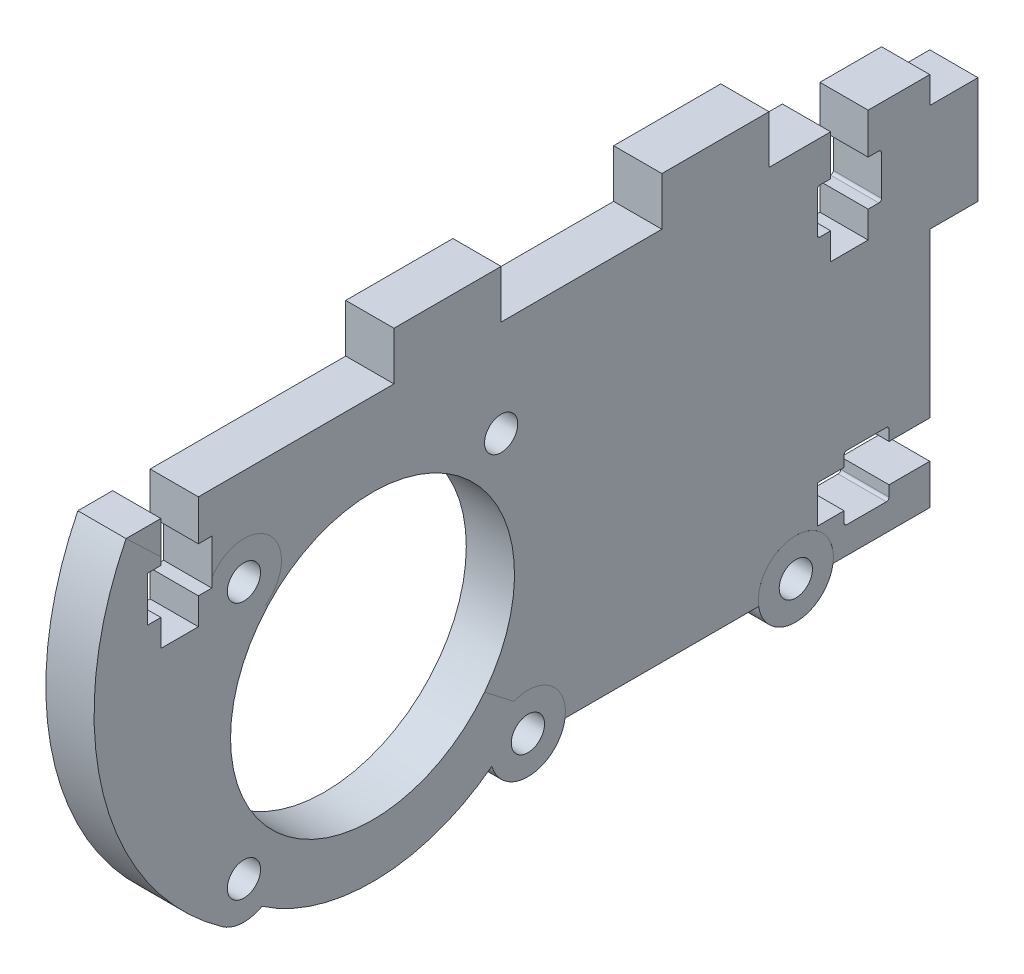
SolidWorks part; units mm, degrees
ref_plane "Front Plane" through (0, 0, 0) normal (0, 0, 1) x (1, 0, 0)
ref_plane "Top Plane" through (0, 0, 0) normal (0, 1, 0) x (1, 0, 0)
ref_plane "Right Plane" through (0, 0, 0) normal (1, 0, 0) x (0, 0, -1)
sketch "Sketch1" plane through (0, 0, 0) normal (1, 0, 0) x (0, 0, -1)
  line L0 (0, 0) -> (0, -35)
  line L1 (0, -35) -> (-75, 0)
  line L2 (-75, 0) -> (0, 0)
  dimension "D1" = 35
  dimension "D2" = 75
extrude "Boss-Extrude1" add sketch "Sketch1" along normal blind 4.5
sketch "Sketch2" plane through (4.5, 0, 0) normal (1, 0, 0) x (0, 0, -1)
  line L0 (0, -35) -> (0, 0) construction
  line L1 (-4.5, -2.5) -> (4.5, -2.5)
  line L2 (-4.5, -2.5) -> (-4.5, -12.5)
  line L3 (-4.5, -12.5) -> (4.5, -12.5)
  line L4 (4.5, -2.5) -> (4.5, -12.5)
  line L5 (-4.5, -2.5) -> (4.5, -12.5) construction
  line L6 (-4.5, -12.5) -> (4.5, -2.5) construction
  line L7 (0, 0) -> (-75, 0) construction
  point P0 (0, -7.5)
  dimension "D1" = 10
  dimension "D2" = 7.5
  dimension "D3" = 4.5
extrude "Boss-Extrude2" add sketch "Sketch2" against normal through all
sketch "Sketch3" plane through (4.5, 0, 0) normal (1, 0, 0) x (0, 0, -1)
  line L0 (0, -35) -> (-40, -35)
  line L1 (0, -25) -> (-75, 0)
  line L4 (0, -35) -> (0, -12.5) construction
  line L5 (0, -25) -> (0, -35)
  line L6 (-75, 0) -> (-40, -35)
  dimension "D1" = 40
  dimension "D2" = 10
extrude "Boss-Extrude3" add sketch "Sketch3" against normal through all
sketch "Sketch4" plane through (4.5, 0, 0) normal (1, 0, 0) x (0, 0, -1)
  line L0 (0, -29.5) -> (-10.5, -29.5) construction
  line L1 (0, -35) -> (0, -12.5) construction
  line L2 (0, -27.75) -> (-10.5, -27.75) construction
  line L3 (-10.5, -27.75) -> (-10.5, -31.25) construction
  line L4 (0, -31.25) -> (0, -27.75)
  line L5 (0, -27.75) -> (-3.8, -27.75)
  line L6 (-3.8, -27.75) -> (-3.8, -26.75)
  line L7 (-4.05, -26.5) -> (-7.75, -26.5)
  line L8 (-8, -26.75) -> (-8, -27.75)
  line L9 (-8, -27.75) -> (-10.5, -27.75)
  line L10 (-10.5, -27.75) -> (-10.5, -31.25)
  line L12 (0, -31.25) -> (-10.5, -31.25) construction
  line L13 (-8, -31.25) -> (-10.5, -31.25)
  line L14 (-8, -32.25) -> (-8, -31.25)
  line L15 (-4.05, -32.5) -> (-7.75, -32.5)
  line L16 (-3.8, -31.25) -> (-3.8, -32.25)
  line L17 (0, -31.25) -> (-3.8, -31.25)
  line L18 (4.5, -12.5) -> (4.5, -2.5) construction
  line L19 (0, -18.5) -> (-56.5, -18.5) construction
  line L20 (-75, 0) -> (-40, -35) construction
  line L37 (0, -31.25) -> (-10.5, -31.25) construction
  arc A0 (-8, -32.25) -> (-7.75, -32.5) centre (-7.75, -32.25) ccw
  arc A1 (-4.05, -32.5) -> (-3.8, -32.25) centre (-4.05, -32.25) ccw
  arc A2 (-3.8, -26.75) -> (-4.05, -26.5) centre (-4.05, -26.75) ccw
  arc A3 (-7.75, -26.5) -> (-8, -26.75) centre (-7.75, -26.75) ccw
  point P10 (4.5, -7.5)
  point P20 (-8, -32.5)
  point P23 (-3.8, -32.5)
  point P26 (-3.8, -26.5)
  point P29 (-8, -26.5)
  dimension "D7" = 0.25
  dimension "D1" = 10.5
  dimension "D2" = 1.75
  dimension "D3" = 3
  dimension "D4" = 4.2
  dimension "D5" = 8
  dimension "D6" = 22
extrude "Cut-Extrude1" cut sketch "Sketch4" against normal through all
sketch "Sketch5" plane through (4.5, 0, 0) normal (1, 0, 0) x (0, 0, -1)
  line L0 (0, 0) -> (-75, 0) construction
  line L1 (-25, 4.5) -> (-15, 4.5)
  line L2 (-25, 4.5) -> (-25, 0)
  line L3 (0, 0) -> (-75, 0) construction
  line L4 (-15, 4.5) -> (-15, 0)
  line L5 (-25, 4.5) -> (-20, 0) construction
  line L6 (-20, 0) -> (-15, 4.5) construction
  line L7 (-32.5, 0) -> (-32.5, 4.5) construction
  line L8 (-45, 0) -> (-50, 4.5) construction
  line L9 (-40, 4.5) -> (-45, 0) construction
  line L10 (-50, 4.5) -> (-50, 0)
  line L12 (-40, 4.5) -> (-40, 0)
  line L13 (-40, 4.5) -> (-50, 4.5)
  line L14 (-20, 0) -> (-15, 4.5) construction
  line L15 (-15, 0) -> (-25, 0)
  line L16 (-40, 0) -> (-50, 0)
  point P0 (-20, 0)
  point P14 (-45, 0)
  dimension "D3" = 4.5
  dimension "D1" = 20
  dimension "D2" = 10
  dimension "D4" = 25
  dimension "D5" = 5
extrude "Boss-Extrude4" add sketch "Sketch5" against normal through all
sketch "Sketch8" [suppressed] plane through (4.5, 0, 0) normal (1, 0, 0) x (0, 0, -1)
  line L0 (-15, -30) -> (-27, -30) construction
  line L1 (-15, -35) -> (-27, -35)
  line L2 (-15, -25) -> (-27, -25)
  line L3 (-15, -35) -> (0, -35) construction
  line L4 (-15, -25) -> (-15, -35)
  arc A1 (-27, -25) -> (-27, -35) centre (-27, -30) ccw
  dimension "D5" = 5
  dimension "D1" = 0
  dimension "D2" = 12
  dimension "D3" = 0
  dimension "D4" = 10
extrude "Boss-Extrude5" [suppressed] add sketch "Sketch8" against normal up to surface (4.5 mm away) up to face at (0, -17.3125, 13.4469)
sketch "Sketch9" [suppressed] plane through (4.5, 0, 0) normal (1, 0, 0) x (0, 0, -1)
  line L0 (-27, -30) -> (-22, -30) construction
  line L1 (-27, -27) -> (-22, -27)
  line L2 (-27, -33) -> (-22, -33)
  arc A0 (-27, -27) -> (-27, -33) centre (-27, -30) ccw
  arc A1 (-22, -33) -> (-22, -27) centre (-22, -30) ccw
  point P3 (-24.5, -30)
  dimension "D1" = 3
  dimension "D2" = 5
extrude "Cut-Extrude3" [suppressed] cut sketch "Sketch9" against normal through all
sketch "Sketch10" plane through (0, 0, 0) normal (-1, 0, 0) x (0, 0, 1)
  line L0 (40, -35) -> (75, -12)
  line L1 (75, -12) -> (75, 0)
  line L3 (75, 0) -> (40, -35)
  dimension "D1" = 12
extrude "Boss-Extrude6" [suppressed] add sketch "Sketch10" against normal through all
sketch "Sketch6" plane through (4.5, 0, 0) normal (1, 0, 0) x (0, 0, -1)
  line L0 (-32.5, 0) -> (-32.5, -10.5) construction
  line L1 (-25, 0) -> (-40, 0) construction
  line L2 (-30.75, -10.5) -> (-34.25, -10.5) construction
  line L3 (-34.25, -10.5) -> (-34.25, 0) construction
  line L4 (-30.75, 0) -> (-34.25, 0)
  line L5 (-34.25, 0) -> (-34.25, -3.8)
  line L6 (-34.25, -3.8) -> (-35.25, -3.8)
  line L7 (-35.5, -4.05) -> (-35.5, -7.75)
  line L8 (-35.25, -8) -> (-34.25, -8)
  line L9 (-34.25, -8) -> (-34.25, -10.5)
  line L10 (-34.25, -10.5) -> (-30.75, -10.5)
  line L11 (-30.75, -10.5) -> (-30.75, 0) construction
  line L12 (-30.75, -8) -> (-30.75, -10.5)
  line L13 (-29.75, -8) -> (-30.75, -8)
  line L14 (-29.5, -4.05) -> (-29.5, -7.75)
  line L15 (-30.75, -3.8) -> (-29.75, -3.8)
  line L16 (-30.75, 0) -> (-30.75, -3.8)
  arc A0 (-35.5, -7.75) -> (-35.25, -8) centre (-35.25, -7.75) ccw
  arc A1 (-35.25, -3.8) -> (-35.5, -4.05) centre (-35.25, -4.05) ccw
  arc A2 (-29.75, -3.8) -> (-29.5, -4.05) centre (-29.75, -4.05) cw
  arc A3 (-29.5, -7.75) -> (-29.75, -8) centre (-29.75, -7.75) cw
  point P12 (-35.5, -8)
  point P15 (-35.5, -3.8)
  point P26 (-29.5, -3.8)
  point P27 (-29.5, -8)
  dimension "D1" = 10.5
  dimension "D2" = 1.75
  dimension "D4" = 4.2
  dimension "D6" = 0.25
  dimension "D3" = 8
  dimension "D5" = 3
extrude "Cut-Extrude2" [suppressed] cut sketch "Sketch6" against normal through all
sketch "Sketch11" plane through (0, 0, 0) normal (-1, 0, 0) x (0, 0, 1)
  line L0 (7.5, 0) -> (7.5, -10.5) construction
  line L1 (0, 0) -> (15, 0) construction
  line L2 (5.75, -10.5) -> (9.25, -10.5)
  line L3 (9.25, -10.5) -> (9.25, -8)
  line L4 (9.25, -8) -> (10.25, -8)
  line L5 (10.5, -7.75) -> (10.5, -4.05)
  line L6 (10.25, -3.8) -> (9.25, -3.8)
  line L7 (9.25, -3.8) -> (9.25, 0)
  line L8 (9.25, 0) -> (5.75, 0)
  line L9 (9.25, -8) -> (9.25, -3.8) construction
  line L10 (0, 0) -> (15, 0) construction
  line L11 (5.75, -8) -> (5.75, -3.8) construction
  line L12 (5.75, -3.8) -> (5.75, 0)
  line L13 (4.75, -3.8) -> (5.75, -3.8)
  line L14 (4.5, -7.75) -> (4.5, -4.05)
  line L15 (5.75, -8) -> (4.75, -8)
  line L16 (5.75, -10.5) -> (5.75, -8)
  arc A0 (10.5, -4.05) -> (10.25, -3.8) centre (10.25, -4.05) ccw
  arc A1 (4.75, -3.8) -> (4.5, -4.05) centre (4.75, -4.05) ccw
  arc A2 (10.25, -8) -> (10.5, -7.75) centre (10.25, -7.75) ccw
  arc A3 (4.5, -7.75) -> (4.75, -8) centre (4.75, -7.75) ccw
  point P11 (7.5, 0)
  point P22 (10.5, -3.8)
  point P25 (4.5, -3.8)
  point P28 (10.5, -8)
  point P31 (4.5, -8)
  dimension "D7" = 0.25
  dimension "D1" = 10.5
  dimension "D3" = 3
  dimension "D8" = 0.25
  dimension "D2" = 4.2
  dimension "D4" = 8
  dimension "D5" = 1.75
  dimension "D6" = 0
extrude "Cut-Extrude4" cut sketch "Sketch11" against normal through all
sketch "Sketch12" plane through (0, 0, 0) normal (-1, 0, 0) x (0, 0, 1)
  line L0 (52, -21) -> (40, -9) construction
  line L1 (52, -21) -> (52, -7.75) construction
  line L2 (52, -21) -> (64, -9) construction
  line L3 (52, -21) -> (38.75, -21) construction
  line L4 (52, -21) -> (40, -33) construction
  line L5 (52, -21) -> (40, -9) construction
  line L6 (0, -27.75) -> (0, -12.5) construction
  line L7 (25, 0) -> (40, 0) construction
  circle A0 centre (52, -21) radius 13.25
  circle A1 centre (40, -9) radius 1.55
  circle A2 centre (64, -9) radius 1.55
  circle A3 centre (40, -33) radius 1.55
  dimension "D1" = 26.5
  dimension "D2" = 3.1
  dimension "D3" = 12
  dimension "D4" = 45
  dimension "D5" = 52
  dimension "D6" = 21
extrude "Cut-Extrude5" cut sketch "Sketch12" against normal through all
sketch "Sketch13" plane through (0, 0, 0) normal (-1, 0, 0) x (0, 0, 1)
  line L0 (61.7849, -12.0659) -> (65.4774, -8.6946)
  line L1 (41.5411, -29.1347) -> (37.5943, -32.2044)
  line L2 (0, -35) -> (100, -35) construction
  line L6 (52, -21) -> (75, 0) construction
  line L7 (52, -21) -> (34, -35) construction
  arc A0 (41.5411, -29.1347) -> (61.7849, -12.0659) centre (52, -21) ccw
  arc A1 (37.5943, -32.2044) -> (65.4774, -8.6946) centre (52, -21) ccw
  circle A3 centre (52, -21) radius 13.25 construction
  dimension "D1" = 5
  dimension "D2" = 100
  dimension "D3" = 18
extrude "Boss-Extrude7" add sketch "Sketch13" against normal through all
sketch "Sketch14" plane through (0, 0, 0) normal (-1, 0, 0) x (0, 0, 1)
  line L0 (52, -7.75) -> (52, -34.25) construction
  line L1 (52, -21) -> (64, -33) construction
  circle A1 centre (64, -33) radius 3.5
  arc A3 (61.7849, -12.0659) -> (41.5411, -29.1347) centre (52, -21) ccw construction
  dimension "D2" = 7
  dimension "D1" = 45
  dimension "D3" = 12
extrude "Boss-Extrude8" add sketch "Sketch14" against normal through all
sketch "Sketch15" plane through (0, 0, 0) normal (-1, 0, 0) x (0, 0, 1)
  line L0 (66.4749, -35.4749) -> (52, -21) construction
  circle A1 centre (64, -33) radius 1.55
  arc A2 (62.305, -36.0622) -> (67.0622, -31.305) centre (64, -33) ccw construction
  arc A4 (62.305, -36.0622) -> (67.0622, -31.305) centre (64, -33) ccw construction
  dimension "D1" = 3.1
extrude "Cut-Extrude6" cut sketch "Sketch15" against normal through all
sketch "Sketch16" [suppressed] plane through (4.5, 0, 0) normal (1, 0, 0) x (0, 0, -1)
  line L0 (0, -34.5) -> (-39, -34.5) construction
  line L1 (0, -27.75) -> (0, -12.5) construction
  line L2 (-15, -34.5) -> (-39, -34.5) construction
  line L3 (-15, -38.5) -> (-39, -38.5)
  line L4 (-15, -30.5) -> (-39, -30.5)
  arc A0 (-15, -38.5) -> (-15, -30.5) centre (-15, -34.5) ccw
  arc A1 (-39, -30.5) -> (-39, -38.5) centre (-39, -34.5) ccw
  point P5 (-27, -34.5)
  point P12 (0, -20.125)
  dimension "D1" = 4
  dimension "D2" = 34.5
  dimension "D3" = 39
  dimension "D4" = 15
extrude "Boss-Extrude9" [suppressed] add sketch "Sketch16" against normal through all
sketch "Sketch17" [suppressed] plane through (4.5, 0, 0) normal (1, 0, 0) x (0, 0, -1)
  line L0 (-43, -34.5) -> (0, -34.5) construction
  line L1 (0, -27.75) -> (0, -12.5) construction
  line L2 (-26.5, -34.5) -> (-26.5, -20.0064) construction
  arc A0 (-42.1823, -32.0766) -> (-39, -38.5) centre (-39, -34.5) ccw construction
  circle A1 centre (-39, -34.5) radius 1.55
  circle A2 centre (-14, -34.5) radius 1.55
  dimension "D1" = 3.1
  dimension "D2" = 12.5
extrude "Cut-Extrude7" [suppressed] cut sketch "Sketch17" against normal through all
sketch "Sketch18" [suppressed] plane through (4.5, 0, 0) normal (1, 0, 0) x (0, 0, -1)
  line L0 (-15, -38.5) -> (0, -35)
  line L1 (0, -35) -> (-11.0314, -35)
  line L2 (-11.0314, -35) -> (-15, -38.5)
extrude "Boss-Extrude10" [suppressed] add sketch "Sketch18" against normal through all
sketch "Sketch20" [suppressed] plane through (4.5, 0, 0) normal (1, 0, 0) x (0, 0, -1)
  line L0 (0, -35) -> (0, -31.25) construction
  line L1 (-9, -38) -> (-58.0081, -38)
  line L2 (-60.773, -36.1642) -> (-76, 0)
  line L3 (-76, 0) -> (-40, -35)
  line L4 (-40, -35) -> (-6, -35)
  line L5 (-9, -38) -> (-6, -35)
  line L6 (-60.773, -36.1642) -> (-60, -38) construction
  line L7 (-60, -38) -> (-58.0081, -38) construction
  arc A1 (-58.0081, -38) -> (-60.773, -36.1642) centre (-58.0081, -35) cw
  point P0 (0, -33.125)
  point P14 (-60, -38)
  dimension "D3" = 6
  dimension "D4" = 3
  dimension "D1" = 60
  dimension "D2" = 3
  dimension "D5" = 135
extrude "Boss-Extrude11" [suppressed] add sketch "Sketch20" against normal through all
sketch "Sketch21" [suppressed] plane through (4.5, 0, 0) normal (1, 0, 0) x (0, 0, -1)
  line L0 (0, -34.5) -> (-61.4737, -34.5) construction
  line L1 (0, -35) -> (0, -31.25) construction
  line L2 (-76, 0) -> (-60.773, -36.1642) construction
  line L3 (0, -27.75) -> (0, -12.5) construction
  circle A0 centre (-51, -34.5) radius 1.55
  circle A1 centre (-26, -34.5) radius 1.55
  dimension "D2" = 3.1
  dimension "D3" = 3.1
  dimension "D1" = 25
  dimension "D4" = 34.5
  dimension "D5" = 26
extrude "Cut-Extrude8" [suppressed] cut sketch "Sketch21" against normal through all
sketch "Sketch22" [suppressed] plane through (4.5, 0, 0) normal (1, 0, 0) x (0, 0, -1)
  line L0 (0, -27.75) -> (0, -12.5) construction
  line L1 (-25, 0) -> (-35, 0) construction
  circle A0 centre (-50, -18) radius 13.25
  dimension "D3" = 26.5
  dimension "D1" = 52
  dimension "D2" = 18
extrude "Cut-Extrude9" [suppressed] cut sketch "Sketch22" against normal through all
sketch "Sketch23" plane through (4.5, 0, 0) normal (1, 0, 0) x (0, 0, -1)
  line L0 (-52, -7.75) -> (-52, -34.25) construction
  arc A0 (-41.5411, -29.1347) -> (-61.7849, -12.0659) centre (-52, -21) ccw construction
  arc A1 (-61.7849, -12.0659) -> (-41.5411, -29.1347) centre (-52, -21) ccw construction
sketch "Sketch24" plane through (4.5, 0, 0) normal (1, 0, 0) x (0, 0, -1)
  line L0 (-65.25, -21) -> (-38.75, -21) construction
  arc A0 (-61.7849, -12.0659) -> (-41.5411, -29.1347) centre (-52, -21) ccw construction
  arc A1 (-41.5411, -29.1347) -> (-61.7849, -12.0659) centre (-52, -21) ccw construction
ref_plane "Plane1" through (0, -21, 0) normal (0, -1, 0) x (-1, 0, 0)
ref_plane "Plane2" through (0, 0, 52) normal (0, 0, -1) x (-1, 0, 0)
mirror "Mirror1" about plane through (0, -21, 0) normal (0, -1, 0) of "Cut-Extrude6", "Boss-Extrude8"
sketch "Sketch25" plane through (0, 0, 0) normal (-1, 0, 0) x (0, 0, 1)
  line L0 (12.5, -34.5) -> (37.5, -34.5) construction
  line L1 (40, -35) -> (0, -35) construction
  line L2 (25, -34.5) -> (25, -29.726) construction
  line L3 (0, -35) -> (0, -31.25) construction
  circle A0 centre (12.5, -34.5) radius 3.5
  circle A1 centre (37.5, -34.5) radius 3.5
  dimension "D2" = 7
  dimension "D3" = 7
  dimension "D1" = 25
  dimension "D4" = 0.5
  dimension "D5" = 25
extrude "Boss-Extrude12" add sketch "Sketch25" against normal through all
sketch "Sketch26" plane through (0, 0, 0) normal (-1, 0, 0) x (0, 0, 1)
  circle A0 centre (12.5, -34.5) radius 1.55
  circle A1 centre (37.5, -34.5) radius 1.55
  dimension "D2" = 3.1
  dimension "D1" = 3.1
extrude "Cut-Extrude10" cut sketch "Sketch26" against normal through all
mirror "Mirror2" [suppressed] about plane through (0, 0, 52) normal (0, 0, -1)
sketch "Sketch27" plane through (0, 0, 0) normal (-1, 0, 0) x (0, 0, 1)
  line L0 (75, 0) -> (70.25, -21)
  line L1 (70.25, -21) -> (65.55, -9)
  line L2 (65.55, -9) -> (75, 0)
  line L4 (62.45, -9) -> (65.55, -9) construction
  arc A0 (67.0622, -31.305) -> (67.0622, -10.695) centre (52, -21) ccw construction
  circle A1 centre (64, -9) radius 1.55 construction
extrude "Boss-Extrude13" add sketch "Sketch27" against normal through all contours L2 L1 L0 region at (0, -10, 70.2667)
sketch "Sketch29" plane through (0, 0, 0) normal (-1, 0, 0) x (0, 0, 1)
  line L0 (65.25, -21) -> (66.0278, -35.8527)
  line L1 (65.25, -21) -> (75, 0)
  line L2 (52, -21) -> (65.25, -21) construction
  arc A0 (66.0278, -35.8527) -> (75, 0) centre (49.5575, -12.682) ccw
  arc A1 (62.305, -36.0622) -> (67.0622, -31.305) centre (64, -33) ccw construction
  arc A2 (34.0359, -35) -> (40.8658, -35.46) centre (37.5, -34.5) ccw construction
  circle A3 centre (52, -21) radius 13.25 construction
extrude "Boss-Extrude14" add sketch "Sketch29" against normal through all
sketch "Sketch28" plane through (0, 0, 0) normal (-1, 0, 0) x (0, 0, 1)
  line L0 (70, 0) -> (70, -10.5) construction
  line L1 (50, 0) -> (75, 0) construction
  line L2 (71.75, -10.5) -> (68.25, -10.5) construction
  line L3 (68.25, -10.5) -> (68.25, 0) construction
  line L4 (71.75, 0) -> (68.25, 0)
  line L5 (68.25, 0) -> (68.25, -3.8)
  line L6 (68.25, -3.8) -> (67, -3.8)
  line L7 (67, -3.8) -> (67, -8)
  line L8 (67, -8) -> (68.25, -8)
  line L9 (68.25, -8) -> (68.25, -10.5)
  line L10 (68.25, -10.5) -> (71.75, -10.5)
  line L11 (71.75, -10.5) -> (71.75, 0) construction
  line L12 (71.75, -8) -> (71.75, -10.5)
  line L13 (73, -8) -> (71.75, -8)
  line L14 (73, -3.8) -> (73, -8)
  line L15 (71.75, -3.8) -> (73, -3.8)
  line L16 (71.75, 0) -> (71.75, -3.8)
  dimension "D1" = 10.5
  dimension "D2" = 1.75
  dimension "D4" = 4.2
  dimension "D3" = 8
  dimension "D5" = 3
  dimension "D6" = 70
extrude "Cut-Extrude11" cut sketch "Sketch28" against normal through all contours L6 L7 L8 L9 L10 L12 L13 L14 L15 L16 L4 L5
equation "\"X-ROD-SPACING\"=45"
equation "\"Y-ROD-SPACING\"=75"
equation "\"Z-ROD-SPACING\"=17.5"
equation "\"Y-BED-OFFSET\"=2"
equation "\"Y-BED-ROD-INSET\"=3.5"
equation "\"Y-BED-SCREW-SPACING\"=209"
equation "\"Y-BED-SCREW-CUTOUT-SLOT-HEIGHT\"=2"
equation "\"T-SLOT-NUT-FILLET-RADIUS\"=0.25"
equation "\"T-SLOT-SCREW-SHAFT-RADIUS\"=1.75"
equation "\"T-SLOT-SCREW-SHAFT-CUTOUT-LENGTH\"=10.5"
equation "\"T-SLOT-NUT-DEPTH\"=4.2"
equation "\"T-SLOT-NUT-WIDTH\"=3"
equation "\"T-SLOT-NUT-END-DISTANCE\"=8"
equation "\"ACRYLIC-THICKNESS\"=10"
equation "\"ACRYLIC-THICKNESS2\"=4.5"
equation "\"ACRYLIC-TAB-CUTOUT-SIZE\"=\"ACRYLIC-THICKNESS\"+\"ACRYLIC-TAB-TOLERANCE\"*2"
equation "\"ACRYLIC-TAB-WIDTH\"=\"ACRYLIC-THICKNESS\""
equation "\"ACRYLIC-M3-HOLE\"=3.1"
equation "\"SMOOTHROD-CAP-SCREW-DISTANCE\"=20"
equation "\"FRAME-WIDTH-INNER\"=370"
equation "\"NEMA17-HOLE-SPACING\"=31"
equation "\"NEMA17-CENTRAL-CUTOUT\"=22.5"
equation "\"Z-BRACKET-REACH\"=55"
equation "\"Z-ROD-INSET\"=16"
equation "\"TOP-BRACKET-SPACING\"=40"
equation "\"SMOOTHROD-X-LENGTH\"=350"
equation "\"SMOOTHROD-Y-LENGTH\"=350"
equation "\"SMOOTHROD-Z-LENGTH\"=350"
equation "\"SMOOTHROD-TIGHTENING-HEADROOM\"=.25"
equation "\"LEADSCREW-Z-LENGTH\"=300"
equation "\"SCREW-LENGTH-FRAME\"=\"ACRYLIC-THICKNESS\" + 10"
equation "\"SCREW-LENGTH-MOTOR\"=\"ACRYLIC-THICKNESS\" + 5"
equation "\"SCREW-LENGTH-EXTRUDER\"=28"
equation "\"SCREW-HEAD-RADIUS\"=6"
equation "\"PRINTED-X-SMOOTHROD-DIAMETER\"=8.2"
equation "\"PRINTED-X-SMOOTHROD-CUTOUT\"=10"
equation "\"PRINTED-X-BASE-HEIGHT\"=10"
equation "\"PRINTED-LM8UU-CUTOUT-SIZE\"=15.25"
equation "\"PRINTED-LM8UU-CUTOUT-LENGTH\"=24.5"
equation "\"PRINTED-X-IDLER-HEIGHT\"=16"
equation "\"PSU-MOUNTING-WIDTH\"=95"
equation "\"PSU-MOUNTING-HEIGHT\"=177"
equation "\"Y-BELT-TO-ROD-DISTANCE\"=20"
equation "\"SPOOL-HOLDER-ROD-SPACING\"=150"
equation "\"ACRYLIC-X-CARRIAGE-WIDTH\"=55"
equation "\"ACRYLIC-X-CARRIAGE-HEIGHT\"=75"
equation "\"ACRYLIC-X-CARRIAGE-SCREW-SPACING-X\"=15"
equation "\"ACRYLIC-X-CARRIAGE-SCREW-SPACING-Y\"=33"
equation "\"ACRYLIC-X-CARRIAGE-CENTER-TAB-SPACING\"=14"
equation "\"ACRYLIC-X-CARRIAGE-EXTRUDER-SHELF-DEPTH\"=\"ACRYLIC-X-CARRIAGE-EXTRUDER-OFFSET\" + 28"
equation "\"D2@Sketch1\"=\"ACRYLIC-X-CARRIAGE-DUAL-MOUNT-PLATE-DEPTH\""
equation "\"D1@Boss-Extrude1\"=\"ACRYLIC-THICKNESS2\""
equation "\"D1@Sketch2\"=\"ACRYLIC-TAB-WIDTH\""
equation "\"D3@Sketch2\"=\"ACRYLIC-THICKNESS2\""
equation "\"ACRYLIC-X-CARRIAGE-LM8UU-CUTOUT-WIDTH\"=24.25"
equation "\"ACRYLIC-X-CARRIAGE-EXTRUDER-BRACE-SPACING\"=23"
equation "\"ACRYLIC-X-CARRIAGE-EXTRUDER-BRACE-HEIGHT\"=35"
equation "\"D1@Sketch1\"=\"ACRYLIC-X-CARRIAGE-EXTRUDER-BRACE-HEIGHT\""
equation "\"D1@Sketch4\"=\"T-SLOT-SCREW-SHAFT-CUTOUT-LENGTH\""
equation "\"D2@Sketch4\"=\"T-SLOT-SCREW-SHAFT-RADIUS\""
equation "\"D3@Sketch4\"=\"T-SLOT-NUT-WIDTH\""
equation "\"D4@Sketch4\"=\"T-SLOT-NUT-DEPTH\""
equation "\"D5@Sketch4\"=\"T-SLOT-NUT-END-DISTANCE\""
equation "\"D7@Sketch4\"=\"T-SLOT-NUT-FILLET-RADIUS\""
equation "\"ACRYLIC-X-CARRIAGE-EXTRUDER-BRACE-SCREW-SPACING\"=22"
equation "\"D6@Sketch4\"=\"ACRYLIC-X-CARRIAGE-EXTRUDER-BRACE-SCREW-SPACING\""
equation "\"ACRYLIC-X-CARRIAGE-EXTRUDER-BRACE-TAB-OFFSET\"=20"
equation "\"D1@Sketch5\"=\"ACRYLIC-X-CARRIAGE-EXTRUDER-BRACE-TAB-OFFSET\""
equation "\"D2@Sketch5\"=\"ACRYLIC-TAB-WIDTH\""
equation "\"D3@Sketch5\"=\"ACRYLIC-THICKNESS2\""
equation "\"ACRYLIC-X-CARRIAGE-EXTRUDER-OFFSET\"=26"
equation "\"ACRYLIC-X-CARRIAGE-EXTRUDER-ANGLE\"=90"
equation "\"D1@Sketch6\"=\"T-SLOT-SCREW-SHAFT-CUTOUT-LENGTH\""
equation "\"D2@Sketch6\"=\"T-SLOT-SCREW-SHAFT-RADIUS\""
equation "\"D3@Sketch6\"=\"T-SLOT-NUT-END-DISTANCE\""
equation "\"D4@Sketch6\"=\"T-SLOT-NUT-DEPTH\""
equation "\"D5@Sketch6\"=\"T-SLOT-NUT-WIDTH\""
equation "\"D6@Sketch6\"=\"T-SLOT-NUT-FILLET-RADIUS\""
equation "\"D1@Sketch11\"=\"T-SLOT-SCREW-SHAFT-CUTOUT-LENGTH\""
equation "\"D2@Sketch11\"=\"T-SLOT-NUT-DEPTH\""
equation "\"D3@Sketch11\"=\"T-SLOT-NUT-WIDTH\""
equation "\"D4@Sketch11\"=\"T-SLOT-NUT-END-DISTANCE\""
equation "\"D5@Sketch11\"=\"T-SLOT-SCREW-SHAFT-RADIUS\""
equation "\"D7@Sketch11\"=\"T-SLOT-NUT-FILLET-RADIUS\""
equation "\"D8@Sketch11\"=\"T-SLOT-NUT-FILLET-RADIUS\""
equation "\"D2@Sketch12\"=\"ACRYLIC-M3-HOLE\""
equation "\"D1@Sketch15\"=\"ACRYLIC-M3-HOLE\""
equation "\"D1@Sketch17\"=\"ACRYLIC-M3-HOLE\""
equation "\"D2@Sketch21\"=\"ACRYLIC-M3-HOLE\""
equation "\"D3@Sketch21\"=\"ACRYLIC-M3-HOLE\""
equation "\"ACRYLIC-TAB-TOLERANCE\"=.1"
equation "\"PRINTED-M3-HOLE\"=3.5"
equation "\"PRINTED-M3-NUT-AF\"=6.25"
equation "\"ACRYLIC-X-CARRIAGE-LM8UU-CUTOUT-HEIGHT\"=11.5"
equation "\"ACRYLIC-X-CARRIAGE-DUAL-WIDTH-MULTIPLIER\"=1.65"
equation "\"ACRYLIC-X-CARRIAGE-DUAL-HOTEND-SPACING\"=42"
equation "\"ACRYLIC-X-CARRIAGE-DUAL-WIDTH\"=95"
equation "\"ACRYLIC-X-CARRIAGE-DUAL-HOTEND-SEPARATION\"=35"
equation "\"ACRYLIC-X-CARRIAGE-DUAL-MOUNT-PLATE-DEPTH\"=75"
equation "\"ACRYLIC-X-CARRIAGE-DUAL-MOUNT-BRACE-WIDTH\"=33"
equation "\"ACRYLIC-X-CARRIAGE-DUAL-MOUNT-SCREW-WIDTH\"=40"
equation "\"BLOWER-FAN-WIDTH\"=15"
equation "\"ACRYLIC-X-CARRIAGE-DUAL-FAN-OFFSET\"=52"
equation "\"D5@Sketch12\"=\"ACRYLIC-X-CARRIAGE-DUAL-FAN-OFFSET\""
equation "\"D1@Sketch22\"=\"ACRYLIC-X-CARRIAGE-DUAL-FAN-OFFSET\""
equation "\"D1@Sketch26\"=\"ACRYLIC-M3-HOLE\""
equation "\"D2@Sketch26\"=\"ACRYLIC-M3-HOLE\""
equation "\"ACRYLIC-X-CARRIAGE-DUAL-FAN-HEIGHT\"=21"
equation "\"D6@Sketch12\"=\"ACRYLIC-X-CARRIAGE-DUAL-FAN-HEIGHT\""
equation "\"D1@Sketch28\"=\"T-SLOT-SCREW-SHAFT-CUTOUT-LENGTH\""
equation "\"D2@Sketch28\"=\"T-SLOT-SCREW-SHAFT-RADIUS\""
equation "\"D3@Sketch28\"=\"T-SLOT-NUT-END-DISTANCE\""
equation "\"D4@Sketch28\"=\"T-SLOT-NUT-DEPTH\""
equation "\"D5@Sketch28\"=\"T-SLOT-NUT-WIDTH\""
